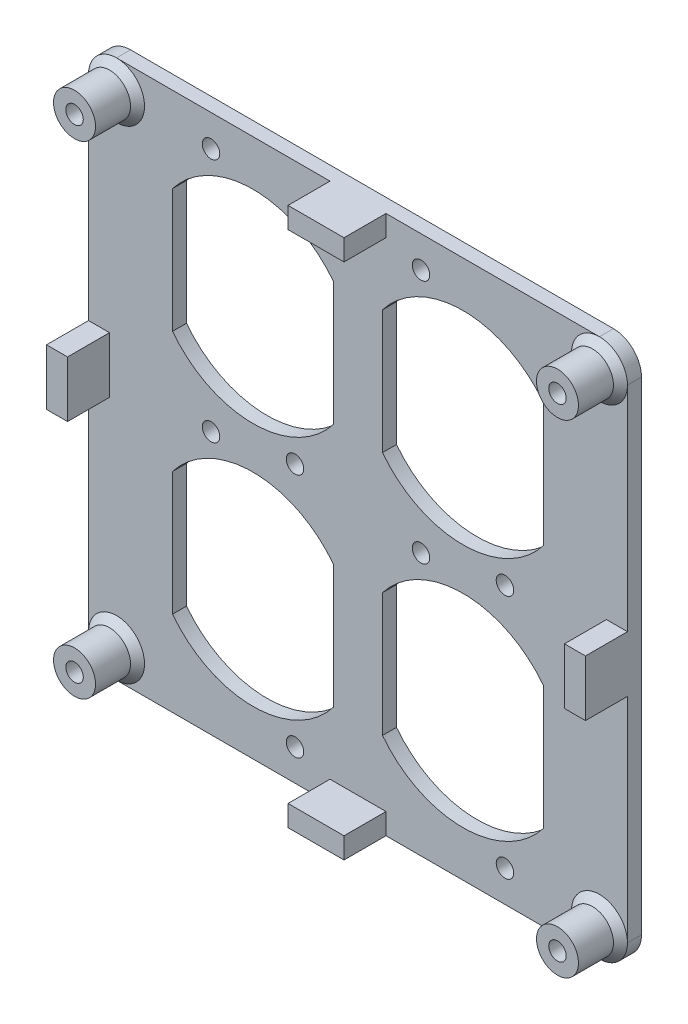
SolidWorks part; units mm, degrees
ref_plane "Front Plane" through (0, 0, 0) normal (0, 0, 1) x (1, 0, 0)
ref_plane "Top Plane" through (0, 0, 0) normal (0, 1, 0) x (1, 0, 0)
ref_plane "Right Plane" through (0, 0, 0) normal (1, 0, 0) x (0, 0, -1)
sketch "Sketch1" plane through (0, 0, 0) normal (0, 0, 1) x (1, 0, 0)
  line L1 (-38.5, -38.5) -> (38.5, -38.5)
  line L2 (-38.5, -38.5) -> (-38.5, 38.5)
  line L3 (-38.5, 38.5) -> (38.5, 38.5)
  line L4 (38.5, -38.5) -> (38.5, 38.5)
  line L5 (-38.5, -38.5) -> (38.5, 38.5) construction
  line L6 (-38.5, 38.5) -> (38.5, -38.5) construction
  point P0 (0, 0)
  dimension "D1" = 77
  dimension "D2" = 77
extrude "Boss-Extrude1" add sketch "Sketch1" along normal blind 2
sketch "Sketch2" plane through (0, 0, 2) normal (0, 0, 1) x (1, 0, 0)
  line L2 (-26.5, 8.6682) -> (-26.5, 26.3318)
  line L4 (-3.5, 8.6682) -> (-3.5, 26.3318)
  line L5 (-26.5, 8.6682) -> (-3.5, 26.3318) construction
  line L6 (-26.5, 26.3318) -> (-3.5, 8.6682) construction
  arc A0 (-26.5, 26.3318) -> (-3.5, 26.3318) centre (-15, 17.5) cw
  arc A1 (-26.5, 8.6682) -> (-3.5, 8.6682) centre (-15, 17.5) ccw
  point P0 (-15, 17.5)
  point P7 (-15, 3)
  point P9 (-15, 32)
  dimension "D1" = 23
  dimension "D2" = 17.5
  dimension "D3" = 15
  dimension "D4" = 29
extrude "Cut-Extrude1" cut sketch "Sketch2" against normal through all
sketch "Sketch3" plane through (0, 0, 2) normal (0, 0, 1) x (1, 0, 0)
  line L0 (-15, 32) -> (-15, 3) construction
  circle A0 centre (-21, 34) radius 1.25
  circle A1 centre (-9, 1) radius 1.25
  arc A2 (-3.5, 26.3318) -> (-26.5, 26.3318) centre (-15, 17.5) ccw construction
  arc A3 (-26.5, 8.6682) -> (-3.5, 8.6682) centre (-15, 17.5) ccw construction
  point P12 (-15, 17.5)
  dimension "D3" = 2.5
  dimension "D1" = 6
  dimension "D2" = 6
  dimension "D4" = 16.5
  dimension "D5" = 16.5
extrude "Cut-Extrude6" cut sketch "Sketch3" against normal through all
pattern_linear "LPattern1" count 2 spacing 35 along (0, -1, 0) count 2 spacing 30 along (1, 0, 0) of "Cut-Extrude1", "Cut-Extrude6"
fillet "Fillet1" radius 4 4 edges at (38.5, -38.5, 1) (38.5, 38.5, 1) (-38.5, 38.5, 1) (-38.5, -38.5, 1)
sketch "Sketch25" plane through (0, 0, 2) normal (0, 0, 1) x (1, 0, 0)
  line L0 (-38.5, 34.5) -> (-38.5, -34.5) construction
  line L1 (34.5, 38.5) -> (-34.5, 38.5) construction
  circle A0 centre (-34.5, 34.5) radius 3
  dimension "D1" = 6
  dimension "D2" = 4
  dimension "D3" = 4
extrude "Boss-Extrude4" add sketch "Sketch25" along normal blind 6
sketch "Sketch26" plane through (0, 0, 8) normal (0, 0, 1) x (1, 0, 0)
  circle A0 centre (-34.5, 34.5) radius 1.25
  dimension "D1" = 2.5
extrude "Cut-Extrude9" cut sketch "Sketch26" against normal blind 3
mirror "Mirror2" about plane through (0, 0, 0) normal (1, 0, 0) of "Cut-Extrude9", "Boss-Extrude4"
mirror "Mirror3" about plane through (0, 0, 0) normal (0, 1, 0) of "Mirror2"
chamfer "Chamfer1" distance 1 distance2 1 4 edges at (31.5, -34.5, 2) (-31.5, -34.5, 2) (-37.5, 34.5, 2) (31.5, 34.5, 2)
sketch "Sketch27" plane through (0, 0, 0) normal (0, 0, 1) x (1, 0, 0)
  line L0 (38.5, -34.5) -> (38.5, 34.5) construction
  line L1 (38.5, -4) -> (35.5, -4)
  line L2 (38.5, -4) -> (38.5, 4)
  line L3 (38.5, 4) -> (35.5, 4)
  line L4 (35.5, -4) -> (35.5, 4)
  line L5 (0, 0) -> (38.5, 0) construction
  dimension "D1" = 8
  dimension "3" = 3
extrude "Boss-Extrude5" add sketch "Sketch27" along normal up to surface (8 mm away) up to face at (31.5, 34.5, 8)
ref_axis "Axis1" through (0, 0, 8.4) along (0, 0, -1)
pattern_circular "CirPattern1" count 4 over 360 about axis through (0, 0, 8.4) along (0, 0, -1) of "Boss-Extrude5"
equation "\"`3\"=10"
